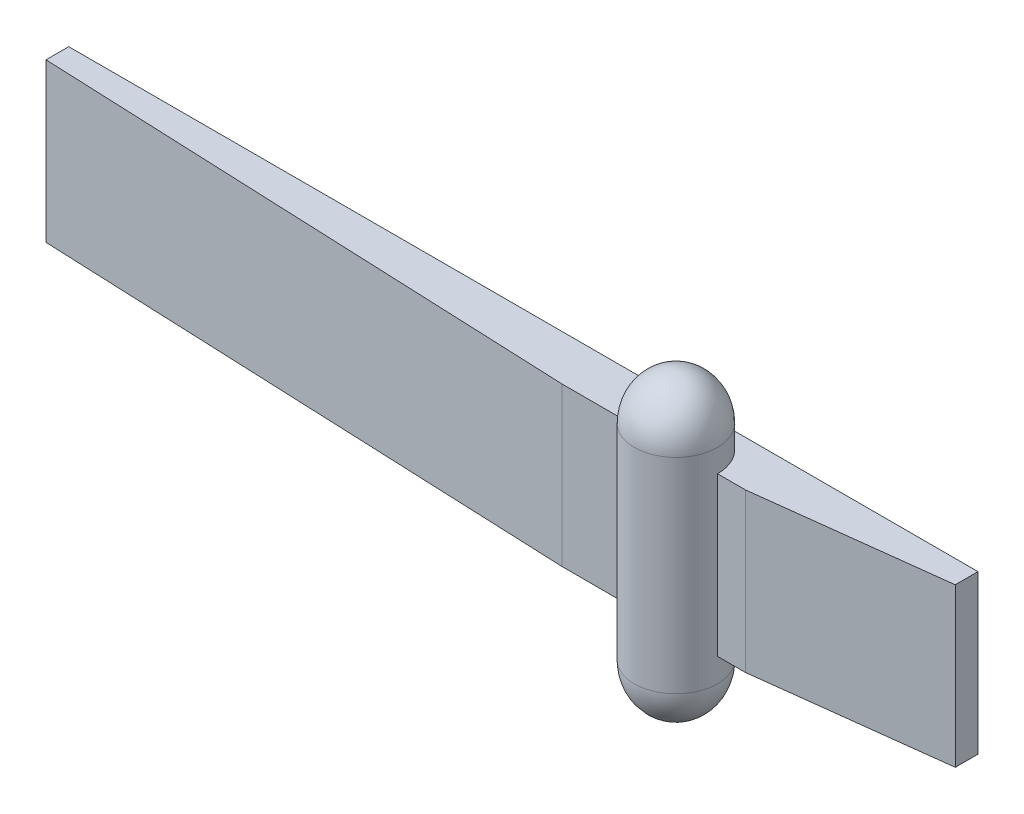
SolidWorks part; units mm, degrees
ref_plane "Front Plane" through (0, 0, 0) normal (0, 0, 1) x (1, 0, 0)
ref_plane "Top Plane" through (0, 0, 0) normal (0, 1, 0) x (1, 0, 0)
ref_plane "Right Plane" through (0, 0, 0) normal (1, 0, 0) x (0, 0, -1)
sketch "Sketch1" plane through (0, 0, 0) normal (0, 0, 1) x (1, 0, 0)
  line L1 (-56.4941, 12.0714) -> (143.4081, 12.0714)
  line L2 (-56.4941, 12.0714) -> (-56.4941, -22.6942)
  line L3 (-56.4941, -22.6942) -> (143.4081, -22.6942)
  line L4 (143.4081, 12.0714) -> (143.4081, -22.6942)
extrude "Boss-Extrude1" add sketch "Sketch1" along normal blind 10
sketch "Sketch2" plane through (0, 12.0714, 0) normal (0, 1, 0) x (1, 0, 0)
  line L0 (143.4081, -10) -> (-56.4941, -10) construction
  circle A0 centre (86.9998, -10) radius 9.1436
extrude "Boss-Extrude2" add sketch "Sketch2" along normal blind 5 and the other way blind 40
dome "Dome1" faces to dome 1 distance 10 reverse direction no elliptical dome yes face at (86.9998, 17.0714, 19.1436) parameters "D1"=10
dome "Dome2" faces to dome 1 distance 10 reverse direction no elliptical dome yes face at (86.9998, -27.9286, 19.1436) parameters "D1"=10
sketch "Sketch3" plane through (0, 12.0714, 0) normal (0, 1, 0) x (1, 0, 0)
  line L0 (-56.4941, -5) -> (61.9887, -10)
  line L1 (-56.4941, -10) -> (-56.4941, 0) construction
  line L2 (77.8562, -10) -> (-56.4941, -10) construction
  line L3 (61.9887, -10) -> (-56.4941, -10)
  line L4 (-56.4941, -10) -> (-56.4941, -5)
  line L5 (143.4081, -5) -> (102.3129, -10)
  line L6 (143.4081, -10) -> (143.4081, 0) construction
  line L7 (143.4081, -10) -> (96.1434, -10) construction
  line L8 (102.3129, -10) -> (143.4081, -10)
  line L9 (143.4081, -10) -> (143.4081, -5)
extrude "Cut-Extrude1" cut sketch "Sketch3" against normal blind 54
